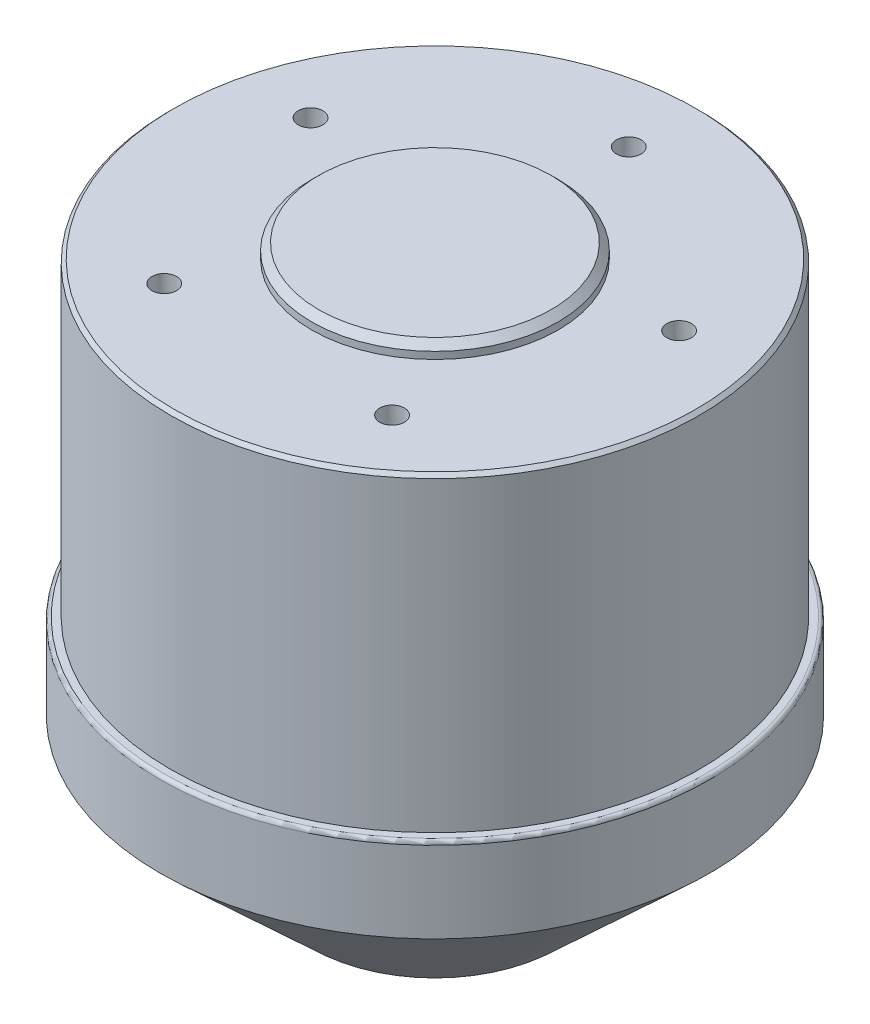
SolidWorks part; units mm, degrees
ref_plane "Front Plane" through (0, 0, 0) normal (0, 0, 1) x (1, 0, 0)
ref_plane "Top Plane" through (0, 0, 0) normal (0, 1, 0) x (1, 0, 0)
ref_plane "Right Plane" through (0, 0, 0) normal (1, 0, 0) x (0, 0, -1)
sketch "Sketch1" plane through (0, 0, 0) normal (0, 1, 0) x (1, 0, 0)
  circle A0 centre (0, 0) radius 39
  circle A1 centre (0, 0) radius 37.5
  circle A2 centre (0, 0) radius 17.5
  dimension "D1" = 78
  dimension "D2" = 75
  dimension "D3" = 35
extrude "Boss-Extrude1" add sketch "Sketch1" along normal blind 76 contours A1 A2 region at (-36.4393, 0, 0)
extrude "Boss-Extrude2" add sketch "Sketch1<3>" along normal blind 78 contours A2 region at (0, 0, 0)
sketch "Sketch1<3>" plane through (0, 0, 0) normal (0, 1, 0) x (1, 0, 0) same geometry as "Sketch1"
extrude "Boss-Extrude3" add sketch "Sketch1<4>" along normal blind 32 contours A0 A1 region at (-37.8969, 0, 0)
sketch "Sketch1<4>" plane through (0, 0, 0) normal (0, 1, 0) x (1, 0, 0) same geometry as "Sketch1"
sketch "Sketch2" plane through (0, 76, 0) normal (0, 1, 0) x (1, 0, 0)
  circle A0 centre (0, 0) radius 27.5
  circle A1 centre (0, 27.5) radius 1.75
  circle A2 centre (26.1541, 8.498) radius 1.75
  circle A3 centre (16.1641, -22.248) radius 1.75
  circle A4 centre (-16.1641, -22.248) radius 1.75
  circle A5 centre (-26.1541, 8.498) radius 1.75
  point P15 (0, 0)
  dimension "D1" = 55
  dimension "D3" = 3.5
  dimension "D2" = 5
extrude "Cut-Extrude1" cut sketch "Sketch2" against normal blind 7 contours A1 | A2 | A3 | A4 | A5
fillet "Fillet1" radius 0.5 1 edges at (0, 32, 39)
chamfer "Chamfer1" distance 0.5 1 edges at (0, 76, 37.5)
chamfer "Chamfer2" distance 21.5 distance2 20 1 edges at (0, 0, 39) first distance on face at (0, 0, 39)
chamfer "Chamfer3" distance 1 1 edges at (0, 78, 17.5)
